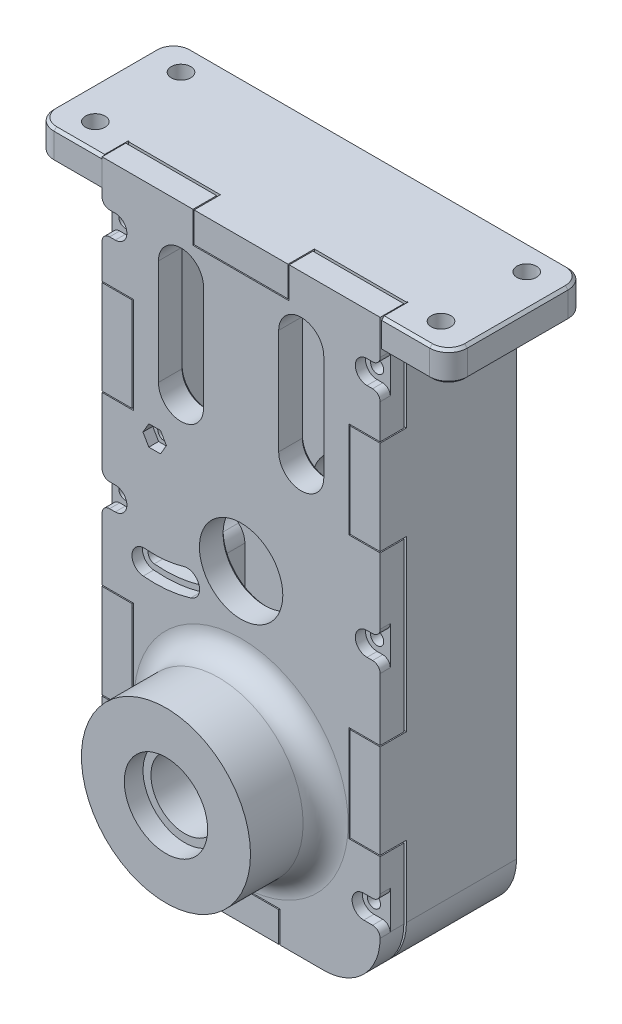
SolidWorks part; units mm, degrees
note: The reader was unsure of these and kept them because the rebuilt part matched: shared geometry of "Sketch4<5>", "Sketch4<6>", "Sketch8<3>", "Sketch14<2>", "Sketch19<3>".
other "Vista explosionada1" [suppressed]
other "Paso de explosión1" [suppressed]
other "Línea de explosión1"
other "Paso de explosión2" [suppressed]
other "Línea de explosión1"
other "Vista explosionada2" [suppressed]
other "Paso de explosión1" [suppressed]
other "Línea de explosión1"
other "Vista explosionada3" [suppressed]
other "Paso de explosión1" [suppressed]
other "Línea de explosión1"
ref_plane "Front Plane" through (0, 0, 0) normal (0, 0, 1) x (1, 0, 0)
ref_plane "Top Plane" through (0, 0, 0) normal (0, 1, 0) x (1, 0, 0)
ref_plane "Right Plane" through (0, 0, 0) normal (1, 0, 0) x (0, 0, -1)
sketch "Sketch1" plane through (0, 0, 0) normal (0, 0, 1) x (1, 0, 0)
  line L0 (15.5, 12) -> (15.5, 19) construction
  line L1 (-15.5, -15.5) -> (15.5, -15.5) construction
  line L2 (-15.5, -15.5) -> (-15.5, 15.5) construction
  line L3 (-15.5, 15.5) -> (15.5, 15.5) construction
  line L4 (15.5, -15.5) -> (15.5, 15.5) construction
  line L5 (-15.5, -15.5) -> (15.5, 15.5) construction
  line L6 (-15.5, 15.5) -> (15.5, -15.5) construction
  line L7 (-21, -21) -> (21, -21)
  line L8 (-21, -21) -> (-21, 21)
  line L9 (-21, 21) -> (21, 21)
  line L10 (21, -21) -> (21, 21)
  line L11 (-21, -21) -> (21, 21) construction
  line L12 (-21, 21) -> (21, -21) construction
  line L13 (13.7, 12) -> (13.7, 19)
  line L14 (17.3, 12) -> (17.3, 19)
  line L15 (-15.5, 12) -> (-15.5, 19) construction
  line L16 (-17.3, 12) -> (-17.3, 19)
  line L17 (-13.7, 12) -> (-13.7, 19)
  line L18 (-15.5, -19) -> (-15.5, -12) construction
  line L19 (-17.3, -19) -> (-17.3, -12)
  line L20 (-13.7, -19) -> (-13.7, -12)
  line L21 (15.5, -19) -> (15.5, -12) construction
  line L22 (13.7, -19) -> (13.7, -12)
  line L23 (17.3, -19) -> (17.3, -12)
  line L24 (0, -3.5) -> (0, 3.5) construction
  line L25 (-11.1, -3.5) -> (-11.1, 3.5)
  line L26 (11.1, -3.5) -> (11.1, 3.5)
  line L28 (-29, 21) -> (29, 21)
  line L29 (-29, 21) -> (-29, -121)
  line L30 (-29, -121) -> (29, -121)
  line L31 (29, 21) -> (29, -121)
  arc A0 (13.7, 12) -> (17.3, 12) centre (15.5, 12) ccw
  arc A1 (17.3, 19) -> (13.7, 19) centre (15.5, 19) ccw
  arc A2 (-17.3, 12) -> (-13.7, 12) centre (-15.5, 12) ccw
  arc A3 (-13.7, 19) -> (-17.3, 19) centre (-15.5, 19) ccw
  arc A4 (-17.3, -19) -> (-13.7, -19) centre (-15.5, -19) ccw
  arc A5 (-13.7, -12) -> (-17.3, -12) centre (-15.5, -12) ccw
  arc A6 (13.7, -19) -> (17.3, -19) centre (15.5, -19) ccw
  arc A7 (17.3, -12) -> (13.7, -12) centre (15.5, -12) ccw
  arc A8 (-11.1, -3.5) -> (11.1, -3.5) centre (0, -3.5) ccw
  arc A9 (11.1, 3.5) -> (-11.1, 3.5) centre (0, 3.5) ccw
  point P0 (0, 0)
  point P6 (0, 0)
  point P13 (15.5, 15.5)
  point P19 (-15.5, 15.5)
  point P27 (-15.5, -15.5)
  point P33 (15.5, -15.5)
  point P41 (0, 0)
  point P50 (0, 21)
  dimension "D4" = 1.8
  dimension "D5" = 11.1
  dimension "D1" = 42
  dimension "D2" = 31
  dimension "D3" = 7
  dimension "D6" = 7
  dimension "D7" = 58
  dimension "D8" = 142
extrude "Boss-Extrude1" add sketch "Sketch1" along normal blind 7 contours L31 L28 L10 L7 L8 L29 L30 | L7 L10 L9 L8 A9 L26 A8 L25 A7 L23 A6 L22 A5 L20 A4 L19 A3 L17 A2 L16 A1 L14 A0 L13
sketch "Sketch3" plane through (0, 0, 0) normal (0, 0, 1) x (1, 0, 0)
  line L8 (37, 29) -> (-37, 29)
  line L9 (-37, 29) -> (-37, -129)
  line L10 (-37, -129) -> (37, -129)
  line L11 (37, -129) -> (37, 29)
  line L12 (37, 29) -> (-37, 29)
  line L13 (-37, 29) -> (-37, -129)
  line L14 (-37, -129) -> (37, -129)
  line L15 (37, -129) -> (37, 29)
  line L16 (29, 21) -> (-29, 21)
  line L17 (-29, 21) -> (-29, -121)
  line L18 (-29, -121) -> (29, -121)
  line L19 (29, -121) -> (29, 21)
  line L20 (29, 21) -> (-29, 21)
  line L21 (-29, 21) -> (-29, -121)
  line L22 (-29, -121) -> (29, -121)
  line L23 (29, -121) -> (29, 21)
  dimension "D1" = 8
  dimension "D2" = 0
extrude "Boss-Extrude2" add sketch "Sketch3" along normal blind 30
sketch "Sketch4" plane through (0, 0, 7) normal (0, 0, -1) x (-1, 0, 0)
  circle A0 centre (0, -48) radius 11.1
  circle A1 centre (0, -92) radius 11.1
  circle A2 centre (0, -48) radius 9
  circle A3 centre (0, -92) radius 9
  dimension "D3" = 22.2
  dimension "D4" = 22.2
  dimension "D5" = 18
  dimension "D1" = 48
  dimension "D2" = 44
extrude "Cut-Extrude2" cut sketch "Sketch4" along normal up to next contours A3 | A2
extrude "Cut-Extrude3" cut sketch "Sketch4<5>" along normal blind 5 contours A0
sketch "Sketch4<5>" plane through (0, 0, 7) normal (0, 0, -1) x (-1, 0, 0) same geometry as "Sketch4"
extrude "Cut-Extrude21" cut sketch "Sketch4<6>" against normal blind 5 from surface at 7 contours A1 A3 starting at face at (9, -92, 0)
sketch "Sketch4<6>" plane through (0, 0, 7) normal (0, 0, -1) x (-1, 0, 0) same geometry as "Sketch4"
sketch "Sketch5" plane through (0, 0, 30) normal (0, 0, 1) x (1, 0, 0)
  line L0 (0, 0) -> (0, -143.1532) construction
  line L1 (-37, 29) -> (-37, -129) construction
  line L2 (-37, 0) -> (-29, 0)
  line L3 (-37, 0) -> (-37, -25)
  line L4 (-37, -25) -> (-29, -25)
  line L5 (-29, 0) -> (-29, -25)
  line L6 (-29, 21) -> (-29, -121) construction
  line L7 (-29, -121) -> (29, -121) construction
  line L8 (-37, -70) -> (-29, -70)
  line L9 (-37, -70) -> (-37, -95)
  line L10 (-37, -95) -> (-29, -95)
  line L11 (-29, -70) -> (-29, -95)
  line L12 (-10, -121) -> (10, -121)
  line L13 (-10, -121) -> (-10, -129)
  line L14 (-10, -129) -> (10, -129)
  line L15 (10, -121) -> (10, -129)
  line L16 (-37, -129) -> (37, -129) construction
  line L17 (29, -70) -> (29, -95)
  line L18 (37, -95) -> (29, -95)
  line L19 (37, -70) -> (37, -95)
  line L20 (37, -70) -> (29, -70)
  line L21 (29, 0) -> (29, -25)
  line L22 (37, -25) -> (29, -25)
  line L23 (37, 0) -> (37, -25)
  line L24 (37, 0) -> (29, 0)
  line L25 (37, 29) -> (-37, 29) construction
  line L26 (-12.5, 29) -> (12.5, 29)
  line L27 (-12.5, 29) -> (-12.5, 21)
  line L28 (-12.5, 21) -> (12.5, 21)
  line L29 (12.5, 29) -> (12.5, 21)
  line L30 (29, 21) -> (-29, 21) construction
  dimension "D1" = 20
  dimension "D2" = 25
  dimension "D3" = 25
  dimension "D4" = 45
  dimension "D5" = 25
extrude "Boss-Extrude4" add sketch "Sketch5" along normal blind 7
sketch "Sketch7" plane through (0, 0, 30) normal (0, 0, 1) x (1, 0, 0)
  line L4 (-10, -121) -> (-10, -129) construction
  line L5 (-10, -129) -> (10, -129) construction
  line L6 (10, -129) -> (10, -121) construction
  line L7 (10, -121) -> (-10, -121) construction
  line L8 (37, -70) -> (29, -70) construction
  line L9 (29, -70) -> (29, -95) construction
  line L10 (29, -95) -> (37, -95) construction
  line L11 (37, -95) -> (37, -70) construction
  line L12 (37, 0) -> (29, 0) construction
  line L13 (29, 0) -> (29, -25) construction
  line L14 (29, -25) -> (37, -25) construction
  line L15 (37, -25) -> (37, 0) construction
  line L16 (-12.5, 29) -> (-12.5, 21) construction
  line L17 (-12.5, 21) -> (12.5, 21) construction
  line L18 (12.5, 21) -> (12.5, 29) construction
  line L19 (12.5, 29) -> (-12.5, 29) construction
  line L20 (-37, 0) -> (-37, -25) construction
  line L21 (-37, -25) -> (-29, -25) construction
  line L22 (-29, -25) -> (-29, 0) construction
  line L23 (-29, 0) -> (-37, 0) construction
  line L24 (-37, -70) -> (-37, -95) construction
  line L25 (-37, -95) -> (-29, -95) construction
  line L26 (-29, -95) -> (-29, -70) construction
  line L27 (-29, -70) -> (-37, -70) construction
  line L28 (-10, -121) -> (-10, -129)
  line L29 (-10, -129) -> (10, -129)
  line L30 (10, -129) -> (10, -121)
  line L31 (10, -121) -> (-10, -121)
  line L32 (37, -70) -> (29, -70)
  line L33 (29, -70) -> (29, -95)
  line L34 (29, -95) -> (37, -95)
  line L35 (37, -95) -> (37, -70)
  line L36 (37, 0) -> (29, 0)
  line L37 (29, 0) -> (29, -25)
  line L38 (29, -25) -> (37, -25)
  line L39 (37, -25) -> (37, 0)
  line L40 (-12.5, 29) -> (-12.5, 21)
  line L41 (-12.5, 21) -> (12.5, 21)
  line L42 (12.5, 21) -> (12.5, 29)
  line L43 (12.5, 29) -> (-12.5, 29)
  line L44 (-37, 0) -> (-37, -25)
  line L45 (-37, -25) -> (-29, -25)
  line L46 (-29, -25) -> (-29, 0)
  line L47 (-29, 0) -> (-37, 0)
  line L48 (-37, -70) -> (-37, -95)
  line L49 (-37, -95) -> (-29, -95)
  line L50 (-29, -95) -> (-29, -70)
  line L51 (-29, -70) -> (-37, -70)
  line L52 (-10.3, -120.7) -> (-10.3, -129.3)
  line L53 (-10.3, -129.3) -> (10.3, -129.3)
  line L54 (10.3, -129.3) -> (10.3, -120.7)
  line L55 (10.3, -120.7) -> (-10.3, -120.7)
  line L56 (37.3, -69.7) -> (28.7, -69.7)
  line L57 (28.7, -69.7) -> (28.7, -95.3)
  line L58 (28.7, -95.3) -> (37.3, -95.3)
  line L59 (37.3, -95.3) -> (37.3, -69.7)
  line L60 (37.3, 0.3) -> (28.7, 0.3)
  line L61 (28.7, 0.3) -> (28.7, -25.3)
  line L62 (28.7, -25.3) -> (37.3, -25.3)
  line L63 (37.3, -25.3) -> (37.3, 0.3)
  line L64 (-12.8, 29.3) -> (-12.8, 20.7)
  line L65 (-12.8, 20.7) -> (12.8, 20.7)
  line L66 (12.8, 20.7) -> (12.8, 29.3)
  line L67 (12.8, 29.3) -> (-12.8, 29.3)
  line L68 (-37.3, 0.3) -> (-37.3, -25.3)
  line L69 (-37.3, -25.3) -> (-28.7, -25.3)
  line L70 (-28.7, -25.3) -> (-28.7, 0.3)
  line L71 (-28.7, 0.3) -> (-37.3, 0.3)
  line L72 (-37.3, -69.7) -> (-37.3, -95.3)
  line L73 (-37.3, -95.3) -> (-28.7, -95.3)
  line L74 (-28.7, -95.3) -> (-28.7, -69.7)
  line L75 (-28.7, -69.7) -> (-37.3, -69.7)
  line L76 (-37, -95) -> (-37, -129)
  line L77 (-37, -129) -> (37, -129)
  line L78 (37, -129) -> (37, 29)
  line L79 (37, 29) -> (-37, 29)
  line L80 (-37, 29) -> (-37, -129)
  dimension "D1" = 0.3
extrude "Boss-Extrude5" add sketch "Sketch7" along normal blind 7 separate body contours L79 L80 L71 L70 L69 L5 L75 L74 L73 L76 L77 L52 L55 L54 L78 L58 L57 L56 L62 L61 L60 L66 L65 L64 | L75 L5 L69 L76
sketch "Sketch28" plane through (0, 0, 37) normal (0, 0, 1) x (1, 0, 0)
  circle A0 centre (0, -92) radius 22.5
  circle A1 centre (0, -92) radius 9
  dimension "D1" = 45
  dimension "D2" = 18
extrude "Boss-Extrude15" add sketch "Sketch28" along normal blind 20
sketch "Sketch8" plane through (0, 0, 57) normal (0, 0, 1) x (1, 0, 0)
  circle A1 centre (0, -92) radius 9
  circle A2 centre (0, -92) radius 9
  circle A3 centre (0, -48) radius 9
  circle A4 centre (0, -48) radius 9
  circle A5 centre (0, -92) radius 11.1
  circle A6 centre (0, -92) radius 11.1
  circle A7 centre (0, -48) radius 11.1
  circle A8 centre (0, -48) radius 11.1
  dimension "D1" = 0
  dimension "D2" = 0
  dimension "D3" = 0
  dimension "D4" = 0
extrude "Cut-Extrude4" cut sketch "Sketch8" against normal up to next contours A4 | A8 A4 | A2
extrude "Cut-Extrude5" cut sketch "Sketch8<3>" against normal blind 5 contours A6 A2
sketch "Sketch8<3>" plane through (0, 0, 57) normal (0, 0, 1) x (1, 0, 0) same geometry as "Sketch8"
sketch "Sketch9" plane through (0, 0, 37) normal (0, 0, 1) x (1, 0, 0)
  line L0 (-23, -29) -> (-25.7507, -58.8736) construction
  line L1 (-23, -29) -> (-14.3595, -57.7288) construction
  line L2 (-23, -29) -> (-20, -58.8496) construction
  line L3 (-37, -25.3) -> (-37, -69.7) construction
  circle A0 centre (-23, -29) radius 1.8
  circle A2 centre (0, -48) radius 9 construction
  arc A3 (-25.7507, -58.8736) -> (-14.3595, -57.7288) centre (-23, -29) ccw construction
  arc A4 (-25.9157, -60.666) -> (-13.8411, -59.4525) centre (-23, -29) ccw
  arc A5 (-25.5857, -57.0812) -> (-14.878, -56.005) centre (-23, -29) ccw
  arc A6 (-25.5857, -57.0812) -> (-25.9157, -60.666) centre (-25.7507, -58.8736) ccw
  arc A7 (-13.8411, -59.4525) -> (-14.878, -56.005) centre (-14.3595, -57.7288) ccw
  circle A8 centre (0, -48) radius 9 construction
  point P8 (-20, -58.8496)
  dimension "D1" = 3.6
  dimension "D4" = 1.8
  dimension "D5" = 30
  dimension "D2" = 23
  dimension "D3" = 19
  dimension "D6" = 22
  dimension "D7" = 17
extrude "Cut-Extrude7" cut sketch "Sketch9" against normal up to surface (7 mm away) contours A4 A7 A5 A6 | A0 up to face at (11.1, -48, 30)
sketch "Sketch10" plane through (0, 0, 37) normal (0, 0, 1) x (1, 0, 0)
  arc A15 (-26.0533, -62.1597) -> (-13.4091, -60.8889) centre (-23, -29) ccw
  arc A16 (-13.4091, -60.8889) -> (-15.31, -54.5686) centre (-14.3595, -57.7288) ccw
  arc A17 (-25.4481, -55.5875) -> (-15.31, -54.5686) centre (-23, -29) ccw
  arc A18 (-25.4481, -55.5875) -> (-26.0533, -62.1597) centre (-25.7507, -58.8736) ccw
  arc A19 (-26.0533, -62.1597) -> (-13.4091, -60.8889) centre (-23, -29) ccw
  arc A20 (-13.4091, -60.8889) -> (-15.31, -54.5686) centre (-14.3595, -57.7288) ccw
  arc A21 (-25.4481, -55.5875) -> (-15.31, -54.5686) centre (-23, -29) ccw
  arc A22 (-25.4481, -55.5875) -> (-26.0533, -62.1597) centre (-25.7507, -58.8736) ccw
  dimension "D1" = 1.5
extrude "Cut-Extrude8" cut sketch "Sketch10" against normal blind 2.8
sketch "Sketch11" plane through (0, 0, 37) normal (0, 0, 1) x (1, 0, 0)
  line L1 (-21.4412, -26.3) -> (-24.5588, -26.3)
  line L2 (-24.5588, -26.3) -> (-26.1177, -29)
  line L3 (-26.1177, -29) -> (-24.5588, -31.7)
  line L4 (-24.5588, -31.7) -> (-21.4412, -31.7)
  line L5 (-21.4412, -31.7) -> (-19.8823, -29)
  line L6 (-19.8823, -29) -> (-21.4412, -26.3)
  circle A0 centre (-23, -29) radius 2.7 construction
  dimension "D1" = 5.4
extrude "Cut-Extrude9" cut sketch "Sketch11" against normal blind 2.6
sketch "Sketch12" plane through (0, 0, 30) normal (0, 0, 1) x (1, 0, 0)
  line L0 (-29, -25) -> (-29, -70) construction
  line L1 (-29, 21) -> (-29, -121) construction
  line L2 (-29, -49.5) -> (-29, -68.5)
  line L3 (-29, -70) -> (-37, -70) construction
  arc A0 (-29, -49.5) -> (-29, -68.5) centre (-23.4547, -59) ccw
  dimension "D1" = 11
  dimension "D2" = 19
  dimension "D3" = 1.5
extrude "Cut-Extrude10" cut sketch "Sketch12" against normal up to surface (23 mm away) up to face at (-11.1, -48, 7)
fillet "Fillet3" radius 15 2 edges at (37, -129, 15) (-37, -129, 15)
fillet "Fillet4" radius 7 2 edges at (-29, -121, 18.5) (29, -121, 18.5)
fillet "Fillet5" radius 15 2 edges at (37, -129, 33.5) (-37, -129, 33.5)
sketch "Sketch14" plane through (0, 0, 37) normal (0, 0, 1) x (1, 0, 0)
  line L0 (33.5, -48) -> (40.5, -48) construction
  line L1 (33.5, -44.9) -> (40.5, -44.9)
  line L2 (33.5, -51.1) -> (40.5, -51.1)
  line L3 (0, 40.9019) -> (0, -142.5578) construction
  line L6 (-33.5, -48) -> (-40.5, -48) construction
  line L9 (32.6421, -109) -> (39.6421, -109) construction
  line L10 (32.6421, -105.9) -> (39.6421, -105.9)
  line L11 (32.6421, -112.1) -> (39.6421, -112.1)
  line L12 (-33.5, -44.9) -> (-40.5, -44.9)
  line L15 (33.5, 14.65) -> (40.5, 14.65) construction
  line L16 (33.5, 17.75) -> (40.5, 17.75)
  line L17 (33.5, 11.55) -> (40.5, 11.55)
  line L18 (37, 0.3) -> (37, 29) construction
  line L19 (37, -69.7) -> (37, -25.3) construction
  line L20 (-33.5, -51.1) -> (-40.5, -51.1)
  line L21 (-32.6421, -109) -> (-39.6421, -109) construction
  line L22 (-32.6421, -105.9) -> (-39.6421, -105.9)
  line L23 (-32.6421, -112.1) -> (-39.6421, -112.1)
  line L24 (-33.5, 14.65) -> (-40.5, 14.65) construction
  line L25 (-33.5, 17.75) -> (-40.5, 17.75)
  line L26 (-33.5, 11.55) -> (-40.5, 11.55)
  line L27 (10.3, -129) -> (22, -129) construction
  arc A0 (33.5, -44.9) -> (33.5, -51.1) centre (33.5, -48) ccw
  arc A1 (40.5, -51.1) -> (40.5, -44.9) centre (40.5, -48) ccw
  arc A6 (32.6421, -105.9) -> (32.6421, -112.1) centre (32.6421, -109) ccw
  arc A7 (39.6421, -112.1) -> (39.6421, -105.9) centre (39.6421, -109) ccw
  arc A10 (33.5, 17.75) -> (33.5, 11.55) centre (33.5, 14.65) ccw
  arc A11 (40.5, 11.55) -> (40.5, 17.75) centre (40.5, 14.65) ccw
  arc A12 (22, -129) -> (37, -114) centre (22, -114) ccw construction
  arc A13 (-33.5, -44.9) -> (-33.5, -51.1) centre (-33.5, -48) cw
  arc A14 (-40.5, -51.1) -> (-40.5, -44.9) centre (-40.5, -48) cw
  arc A15 (-32.6421, -105.9) -> (-32.6421, -112.1) centre (-32.6421, -109) cw
  arc A16 (-39.6421, -112.1) -> (-39.6421, -105.9) centre (-39.6421, -109) cw
  arc A17 (-33.5, 17.75) -> (-33.5, 11.55) centre (-33.5, 14.65) cw
  arc A18 (-40.5, 11.55) -> (-40.5, 17.75) centre (-40.5, 14.65) cw
  circle A20 centre (0, -48) radius 9 construction
  circle A21 centre (33.5, 14.65) radius 1.75
  circle A22 centre (33.5, -48) radius 1.75
  circle A23 centre (32.6421, -109) radius 1.75
  circle A24 centre (-33.5, 14.65) radius 1.75
  circle A25 centre (-33.5, -48) radius 1.75
  circle A26 centre (-32.6421, -109) radius 1.75
  circle A27 centre (0, -48) radius 9 construction
  point P2 (37, -48)
  point P11 (-37, -48)
  point P18 (-36.1421, -109)
  point P23 (36.1421, -109)
  point P32 (-37, 14.65)
  point P35 (37, 14.65)
  dimension "D2" = 3.1
  dimension "D4" = 3.5
  dimension "D1" = 7
  dimension "D3" = 20
extrude "Cut-Extrude11" cut sketch "Sketch14" against normal blind 2.7
extrude "Cut-Extrude12" cut sketch "Sketch14<2>" against normal up to surface (7 mm away) contours A26 | A25 | A24 | A21 | A22 | A23 up to face at (-20.0447, -58.4045, 30)
sketch "Sketch14<2>" plane through (0, 0, 37) normal (0, 0, 1) x (1, 0, 0) same geometry as "Sketch14"
sketch "Sketch15" plane through (0, 0, 37) normal (0, 0, 1) x (1, 0, 0)
  line L0 (0, 0) -> (0, -162.1806) construction
  circle A0 centre (33.5, 14.65) radius 1.5
  circle A1 centre (33.5, -48) radius 1.5
  circle A2 centre (32.6421, -109) radius 1.5
  circle A3 centre (-32.6421, -109) radius 1.5
  circle A4 centre (-33.5, -48) radius 1.5
  circle A5 centre (-33.5, 14.65) radius 1.5
  dimension "D1" = 3
extrude "Cut-Extrude13" cut sketch "Sketch15" against normal blind 16
sketch "Sketch16" plane through (0, 0, 37) normal (0, 0, 1) x (1, 0, 0)
  line L0 (-16, 12.5) -> (-16, -15.5) construction
  line L3 (-10, 12.5) -> (-10, -15.5)
  line L8 (-22, 12.5) -> (-22, -15.5)
  line L9 (0, 0) -> (0, 14.3805) construction
  line L10 (16, 12.5) -> (16, -15.5) construction
  line L11 (10, 12.5) -> (10, -15.5)
  line L12 (22, 12.5) -> (22, -15.5)
  arc A2 (-10, 12.5) -> (-22, 12.5) centre (-16, 12.5) ccw
  arc A3 (-22, -15.5) -> (-10, -15.5) centre (-16, -15.5) ccw
  arc A4 (10, 12.5) -> (22, 12.5) centre (16, 12.5) cw
  arc A5 (22, -15.5) -> (10, -15.5) centre (16, -15.5) cw
  point P3 (-16, -1.5)
  point P12 (16, -1.5)
  dimension "D1" = 10
  dimension "D2" = 6
  dimension "D3" = 28
  dimension "D4" = 12.5
extrude "Cut-Extrude14" cut sketch "Sketch16" against normal up to surface (7 mm away) up to face at (35.25, -48, 30)
fillet "Fillet6" radius 2 12 edges at (37, 17.75, 35.65) (37, 11.55, 35.65) (37, -51.1, 35.65) (37, -44.9, 35.65) (37, -105.9, 35.65) (37, -112.1, 35.65) (-37, 17.75, 35.65) (-37, 11.55, 35.65) (-37, -44.9, 35.65) (-37, -51.1, 35.65) (-37, -105.9, 35.65) (-37, -112.1, 35.65)
sketch "Sketch17" plane through (0, 29, 0) normal (0, 1, 0) x (1, 0, 0)
  line L21 (-55, 0) -> (55, 0)
  line L22 (-55, 0) -> (-55, -29.8)
  line L23 (-55, -29.8) -> (55, -29.8)
  line L24 (55, 0) -> (55, -29.8)
  line L25 (-12.5, -30) -> (-37, -30) construction
  dimension "D1" = 110
  dimension "D2" = 0.2
extrude "Boss-Extrude8" add sketch "Sketch17" against normal blind 8
sketch "Sketch18" plane through (0, 0, 29.8) normal (0, 0, 1) x (1, 0, 0)
  line L5 (-37, 29) -> (-55, 29) construction
  line L6 (-55, 29) -> (-55, 21) construction
  line L7 (-55, 21) -> (-37, 21) construction
  line L13 (-37.2, 29) -> (-55, 29)
  line L14 (-55, 29) -> (-55, 21)
  line L15 (-55, 21) -> (-37.2, 21)
  line L16 (-37.2, 21) -> (-37.2, 29)
  line L17 (-37, 29) -> (-37, 19.75) construction
  line L18 (0, 46.6374) -> (0, 32.4665) construction
  line L19 (37.2, 21) -> (37.2, 29)
  line L20 (55, 21) -> (37.2, 21)
  line L21 (55, 29) -> (55, 21)
  line L22 (37.2, 29) -> (55, 29)
  dimension "D1" = 0.2
extrude "Boss-Extrude10" add sketch "Sketch18" along normal blind 7
sketch "Sketch19" plane through (0, 21, 0) normal (0, -1, 0) x (1, 0, 0)
  line L0 (-55, 36.8) -> (-37.2, 36.8) construction
  line L1 (-40.4574, 29.8) -> (-43.2287, 34.6)
  line L2 (-43.2287, 34.6) -> (-48.7713, 34.6)
  line L3 (-48.7713, 34.6) -> (-51.5426, 29.8)
  line L4 (-51.5426, 29.8) -> (-48.7713, 25)
  line L5 (-48.7713, 25) -> (-43.2287, 25)
  line L6 (-43.2287, 25) -> (-40.4574, 29.8)
  line L7 (-43.2287, 11.8) -> (-48.7713, 11.8)
  line L8 (-48.7713, 11.8) -> (-51.5426, 7)
  line L9 (-51.5426, 7) -> (-48.7713, 2.2)
  line L10 (-48.7713, 2.2) -> (-43.2287, 2.2)
  line L11 (-43.2287, 2.2) -> (-40.4574, 7)
  line L12 (-40.4574, 7) -> (-43.2287, 11.8)
  line L13 (0, 0) -> (0, 48.0866) construction
  line L14 (-22, 0) -> (22, 0) construction
  line L15 (40.4574, 7) -> (43.2287, 11.8)
  line L16 (43.2287, 2.2) -> (40.4574, 7)
  line L17 (48.7713, 2.2) -> (43.2287, 2.2)
  line L18 (51.5426, 7) -> (48.7713, 2.2)
  line L19 (48.7713, 11.8) -> (51.5426, 7)
  line L20 (43.2287, 11.8) -> (48.7713, 11.8)
  line L21 (43.2287, 25) -> (40.4574, 29.8)
  line L22 (48.7713, 25) -> (43.2287, 25)
  line L23 (51.5426, 29.8) -> (48.7713, 25)
  line L24 (48.7713, 34.6) -> (51.5426, 29.8)
  line L25 (43.2287, 34.6) -> (48.7713, 34.6)
  line L26 (40.4574, 29.8) -> (43.2287, 34.6)
  circle A0 centre (-46, 29.8) radius 4.8 construction
  circle A1 centre (-46, 7) radius 4.8 construction
  circle A2 centre (46, 7) radius 4.8 construction
  circle A3 centre (46, 29.8) radius 4.8 construction
  circle A4 centre (-46, 29.8) radius 2.6
  circle A5 centre (-46, 7) radius 2.6
  circle A6 centre (46, 7) radius 2.6
  circle A7 centre (46, 29.8) radius 2.6
  dimension "D5" = 5.2
  dimension "D1" = 9.6
  dimension "D2" = 46
  dimension "D3" = 7
  dimension "D4" = 7
extrude "Cut-Extrude15" cut sketch "Sketch19" against normal blind 2.5 contours L26 L21 L22 L23 L24 L25 A7 | L20 L15 L16 L17 L18 L19 A6 | L11 L12 L7 L8 L9 L10 A5 | L5 L6 L1 L2 L3 L4 A4
extrude "Cut-Extrude16" cut sketch "Sketch19<3>" against normal through all contours A4 | A5 | A6 | A7
sketch "Sketch19<3>" plane through (0, 21, 0) normal (0, -1, 0) x (1, 0, 0) same geometry as "Sketch19"
fillet "Fillet7" radius 5 4 edges at (55, 25, 0) (55, 25, 36.8) (-55, 25, 0) (-55, 25, 36.8)
sketch "Sketch20" [suppressed] plane through (0, 0, 0) normal (0, 0, 1) x (1, 0, 0)
  line L0 (-37, 29) -> (-11, 55)
  line L1 (0, 68) -> (0, 100.437) construction
  line L2 (37, 29) -> (11, 55)
  line L3 (-37, 29) -> (37, 29)
  line L4 (-1, 68) -> (-1, 80)
  line L5 (1, 68) -> (1, 80)
  line L6 (-1, 68) -> (-1, 61.9947) construction
  line L7 (1, 68) -> (1, 61.9947) construction
  line L8 (11, 55) -> (11, 80)
  line L9 (11, 80) -> (-1, 80)
  line L10 (0, 68) -> (0, 61.9947) construction
  line L11 (-11, 55) -> (-11, 80)
  line L12 (-11, 80) -> (1, 80)
  circle A0 centre (0, 68) radius 4.1
  dimension "D1" = 8.2
  dimension "D3" = 12
  dimension "D2" = 68
  dimension "D6" = 25
  dimension "D7" = 80
  dimension "D4" = 1
  dimension "D5" = 1
chamfer "Chamfer1" distance 0.7 angle 45 46 edges at (9, -48, 0) (11.1, -92, 0) (37, -46.5, 0) (0, -129, 0) (-32.6066, -124.6066, 0) (32.6066, -124.6066, 0) (-37, -46.5, 0) (-43.5, 21, 0) (13.7, 15.5, 0) (15.5, 10.2, 0) (17.3, 15.5, 0) (15.5, 20.8, 0) (-17.3, 15.5, 0) (43.6, 21, 36.8) (-15.5, 10.2, 0) (-13.7, 15.5, 0) (-43.6, 29, 36.8) (-15.5, 20.8, 0) (-17.3, -15.5, 0) (-15.5, -20.8, 0) (-13.7, -15.5, 0) (-15.5, -10.2, 0) (13.7, -15.5, 0) (15.5, -20.8, 0) (17.3, -15.5, 0) (15.5, -10.2, 0) (-11.1, 0, 0) (0, -14.6, 0) (11.1, 0, 0) (0, 14.6, 0) (55, 29, 18.4) (55, 21, 18.4) (43.6, 29, 36.8) (0, 29, 0) (-55, 29, 18.4) (-53.5355, 29, 35.3355) (-53.5355, 29, 1.4645) (53.5355, 29, 35.3355) (53.5355, 29, 1.4645) (43.5, 21, 0) (53.5355, 21, 35.3355) (53.5355, 21, 1.4645) (-55, 21, 18.4) (-43.6, 21, 36.8) (-53.5355, 21, 35.3355) (-53.5355, 21, 1.4645)
chamfer "Chamfer2" distance 0.7 angle 45 51 edges at (34.3921, -109, 30) (35.25, 14.65, 30) (-31.75, 14.65, 30) (-31.75, -48, 30) (-30.8921, -109, 30) (-27.5431, -58.7086, 30) (-20.18, -57.0586, 30) (-12.6358, -57.2103, 30) (-19.82, -60.6406, 30) (-21.2, -29, 30) (32.85, -95.3, 30) (28.7, -82.5, 30) (32.85, -69.7, 30) (37, -47.5, 30) (32.85, -25.3, 30) (28.7, -12.5, 30) (32.85, 0.3, 30) (37, 14.65, 30) (24.9, 29, 30) (12.8, 24.85, 30) (0, 20.7, 30) (-12.8, 24.85, 30) (-24.9, 29, 30) (-37, 14.65, 30) (-32.85, 0.3, 30) (-28.7, -12.5, 30) (-32.85, -25.3, 30) (-37, -47.5, 30) (-32.85, -69.7, 30) (-28.7, -82.5, 30) (-32.85, -95.3, 30) (-37, -104.65, 30) (-32.6066, -124.6066, 30) (-16.15, -129, 30) (-10.3, -124.85, 30) (0, -120.7, 30) (10.3, -124.85, 30) (16.15, -129, 30) (32.6066, -124.6066, 30) (37, -104.65, 30) (9, -92, 30) (35.25, -48, 30) (11.1, -48, 30) (16, -21.5, 30) (10, -1.5, 30) (16, 18.5, 30) (22, -1.5, 30) (-16, -21.5, 30) (-22, -1.5, 30) (-16, 18.5, 30) (-10, -1.5, 30)
fillet "Fillet8" radius 5 2 edges at (-29, -49.5, 18.5) (-29, -68.5, 18.5)
fillet "Fillet12" radius 6 1 edges at (22.5, -92, 37)
move or copy body "Sólido-Mover/Copiar5" [suppressed] bodies to move or copy 128 copy no translate (0, 0, 27.0157) parameters "D1"=0, "D2"=0, "D3"=0
move or copy body "Sólido-Mover/Copiar3" [suppressed] bodies to move or copy 128 copy no translate (0, 0, 32.0016) parameters "D1"=0, "D2"=0, "D3"=0
move or copy body "Sólido-Mover/Copiar4" [suppressed] bodies to move or copy 134 copy no translate (0, 0, -25.5467) parameters "D1"=0, "D2"=0, "D3"=0
